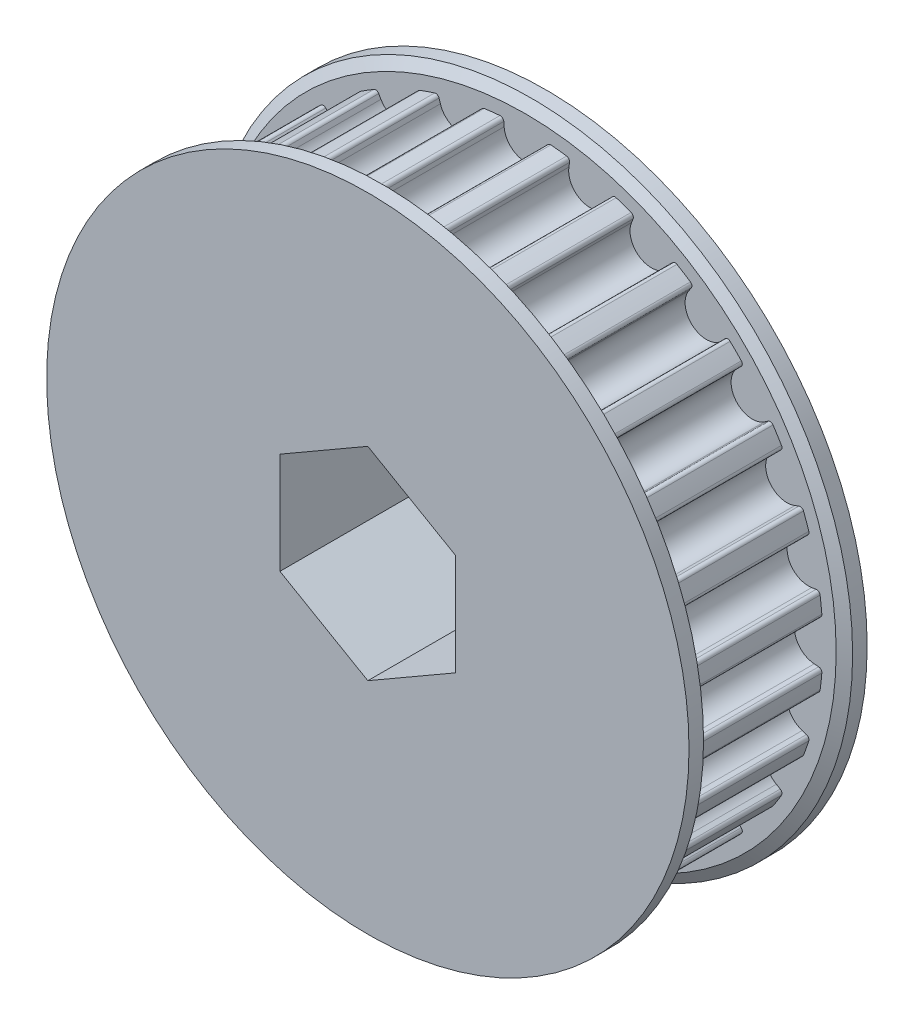
SolidWorks part; units mm, degrees
ref_plane "Front Plane" through (0, 0, 0) normal (0, 0, 1) x (1, 0, 0)
ref_plane "Top Plane" through (0, 0, 0) normal (0, 1, 0) x (1, 0, 0)
ref_plane "Right Plane" through (0, 0, 0) normal (1, 0, 0) x (0, 0, -1)
ref_axis "Centaur" through (0, 0, -4.95) along (0, 0, 1)
sketch "Sketch1" plane through (0, 0, 0) normal (0, 0, 1) x (1, 0, 0)
  line L0 (0, -1000) -> (0, 49000) construction
  line L1 (2.4308, 21.5737) -> (2.6242, 23.29)
  line L2 (1.5797, 21.3965) -> (1.5558, 21.0725)
  line L3 (-1.5797, 21.3965) -> (-1.5558, 21.0725)
  line L4 (-2.4308, 21.5737) -> (-2.6242, 23.29)
  line L5 (2.4308, 21.5737) -> (2.3658, 20.997) construction
  arc A0 (2.4308, 21.5737) -> (1.8547, 21.6308) centre (0, 0) ccw
  circle A1 centre (0, 0) radius 19.6274 construction
  circle A2 centre (0, 0) radius 23.4374 construction
  arc A3 (-1.5558, 21.0725) -> (1.5558, 21.0725) centre (0, 21.1874) ccw
  arc A4 (-2.4948, 22.1416) -> (2.4948, 22.1416) centre (0, 0) cw construction
  arc A5 (-2.4308, 21.5737) -> (-1.8547, 21.6308) centre (0, 0) cw
  arc A6 (-2.6242, 23.29) -> (2.6242, 23.29) centre (0, 0) cw
  arc A7 (1.5797, 21.3965) -> (1.8547, 21.6308) centre (1.833, 21.3778) cw
  arc A8 (-1.5797, 21.3965) -> (-1.8547, 21.6308) centre (-1.833, 21.3778) ccw
  circle A9 centre (0, 0) radius 21.1299 construction
  point P12 (0, 22.2817)
  point P21 (1.5985, 21.6513)
  point P24 (-1.5985, 21.6513)
  point P26 (0, 0)
  point P27 (0, 0)
  dimension "D6" = 3.12
  dimension "D7" = 0.254
  dimension "D1" = 6.429
  dimension "D3" = 0.5715
  dimension "D4" = 2.0828
  dimension "D8" = 0.5803
  dimension "D2" = 5
sketch "Sketch2" plane through (0, 0, 0) normal (0, 0, 1) x (1, 0, 0)
  circle A0 centre (0, 0) radius 23.4374
  circle A1 centre (0, 0) radius 23.4374 construction
extrude "Main Body" add sketch "Sketch2" along normal blind 5
extrude "Toof Cut" cut sketch "Sketch1" along normal through all
pattern_circular "Toof Pattern" count 28 over 360 about axis through (0, 0, -4.95) along (0, 0, 1) of "Toof Cut"
sketch "Sketch3" plane through (0, 0, 5) normal (0, 0, 1) x (1, 0, 0)
  circle A1 centre (0, 0) radius 23.4374
  circle A2 centre (0, 0) radius 23.4374 construction
  circle A3 centre (0, 0) radius 23.4374 construction
extrude "Flange'" add sketch "Sketch3" along normal blind 1.5
chamfer "Chamfer1" distance 0.762 angle 30 1 edges at (23.4374, 0, 5) first distance on face at (0, 0, 5)
mirror "Mirror1" about plane through (0, 0, 0) normal (0, 0, 1) of bodies 104
sketch "Sketch4" plane through (0, 0, 0) normal (0, 0, 1) x (1, 0, 0)
  line L1 (6.4135, 3.7028) -> (0, 7.4057)
  line L2 (0, 7.4057) -> (-6.4135, 3.7028)
  line L3 (-6.4135, 3.7028) -> (-6.4135, -3.7028)
  line L4 (-6.4135, -3.7028) -> (0, -7.4057)
  line L5 (0, -7.4057) -> (6.4135, -3.7028)
  line L6 (6.4135, -3.7028) -> (6.4135, 3.7028)
  circle A0 centre (0, 0) radius 6.4135 construction
  dimension "D1" = 12.827
extrude "Cut-Extrude1" cut sketch "Sketch4" against normal through all both and the other way through all
delete or keep bodies "Body-Delete/Keep 1" [suppressed] type keep bodies bodies 108
equation "\"teeth\"= 28"
equation "\"width\"= 10mm"
equation "\"rim_extra_depth\"= 0mm"
equation "\"D1@Sketch1\"=360/\"teeth\"/2"
equation "\"D1@Main Body\" = \"width\" / 2"
equation "\"D1@Toof Pattern\" = \"teeth\""
equation "\"D1@Sketch3\"=\"rim_extra_depth\""
